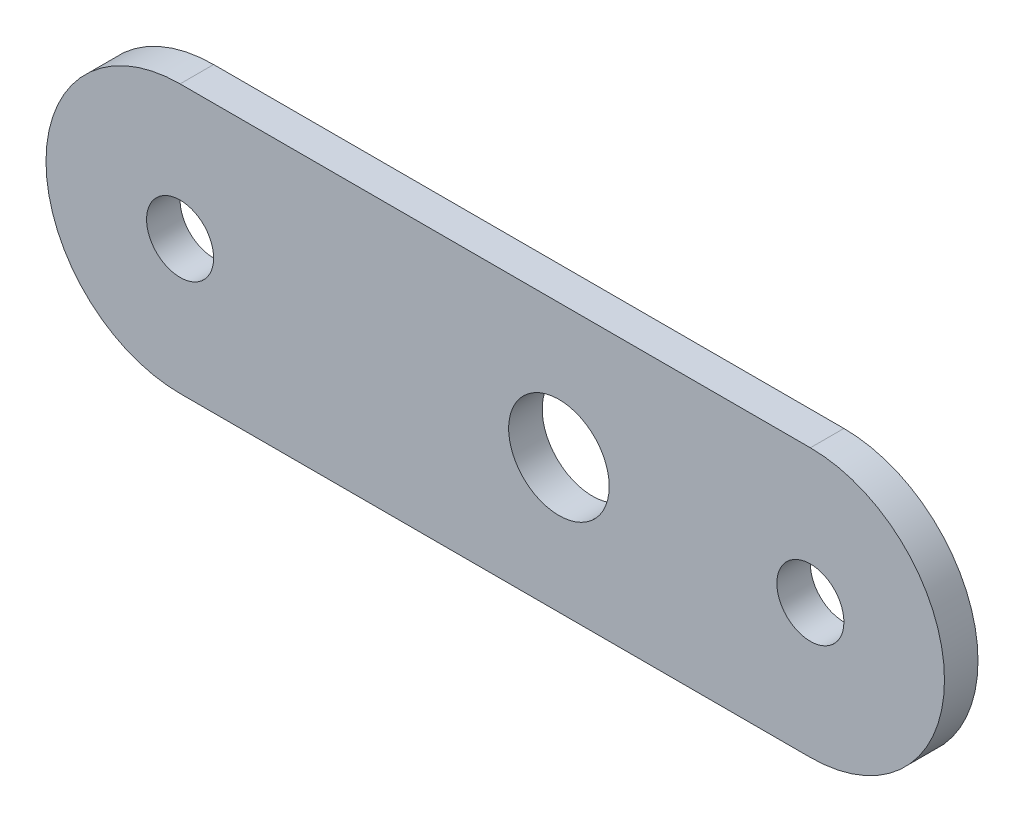
SolidWorks part; units mm, degrees
ref_plane "Спереди" through (0, 0, 0) normal (0, 0, 1) x (1, 0, 0)
ref_plane "Сверху" through (0, 0, 0) normal (0, 1, 0) x (1, 0, 0)
ref_plane "Справа" through (0, 0, 0) normal (1, 0, 0) x (0, 0, -1)
sketch "Sketch1" plane through (0, 0, 0) normal (0, 0, 1) x (1, 0, 0)
  line L0 (0, 0) -> (-11.3, 0)
  line L1 (0, 0) -> (7.5, 0)
  line L2 (-11.3, 4) -> (7.5, 4)
  line L3 (0, 0) -> (0, 12.3009) construction
  line L4 (-11.3, -4) -> (7.5, -4)
  circle A0 centre (0, 0) radius 1.5
  circle A2 centre (-11.3, 0) radius 1
  circle A5 centre (-11.3, 0) radius 4
  circle A10 centre (7.5, 0) radius 1
  circle A11 centre (7.5, 0) radius 4
  point P17 (0, -4)
  point P18 (0, 4)
  dimension "D1" = 11.3
  dimension "D2" = 7.5
extrude "Extrude1" add sketch "Sketch1" against normal blind 1 contours L4 L3 A0 L0 A5 | A0 L3 L2 A5 L0 | L3 A0 L1 A11 L2 | L3 L4 A11 L1 A0 | A11 A10 | A5 A2 region at (-4.3279, 2.2011, 0) region at (-8.5516, -2.7484, 0) region at (-2.0443, -2.2669, 0) region at (2.455, 2.3963, 0) region at (4.7516, -2.7484, 0)
